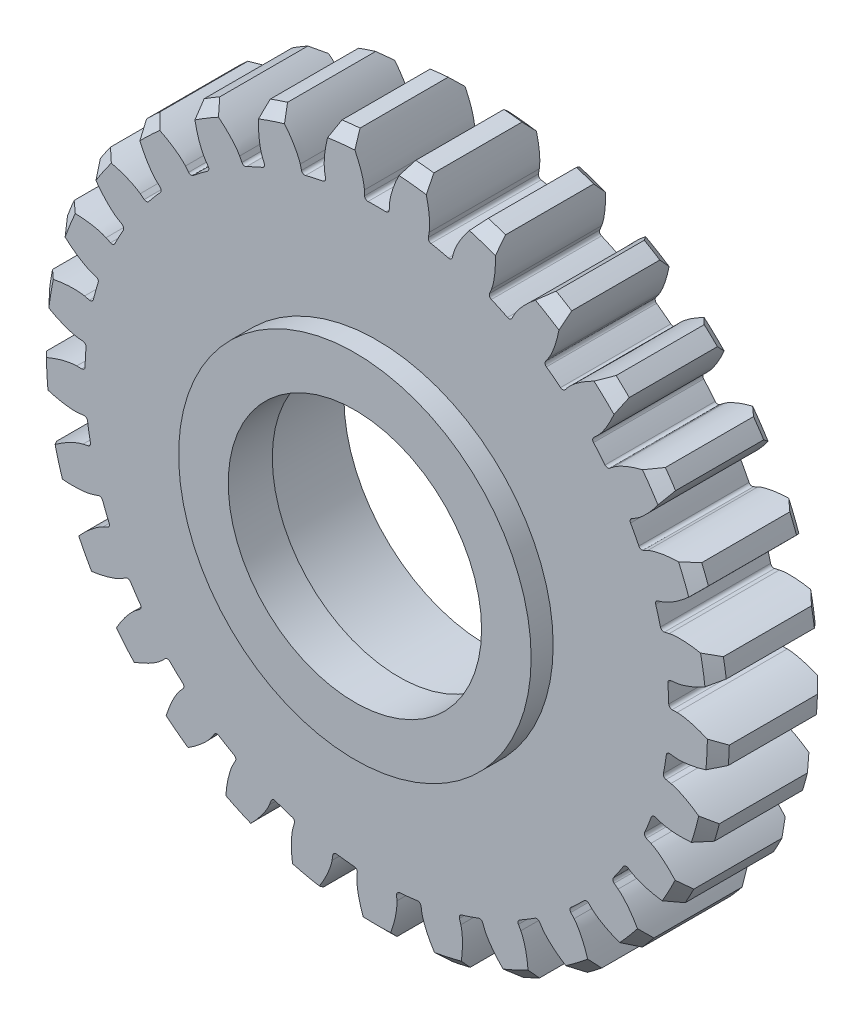
SolidWorks part; units mm, degrees
ref_plane "中间平面" through (0, 0, 0) normal (0, 0, 1) x (1, 0, 0)
ref_plane "上视基准面" through (0, 0, 0) normal (0, 1, 0) x (1, 0, 0)
ref_plane "右视基准面" through (0, 0, 0) normal (1, 0, 0) x (0, 0, -1)
sketch "直齿轮" plane through (0, 0, 0) normal (0, 0, 1) x (1, 0, 0)
  line L0 (0, 0) -> (-1.57, 28.9575) construction
  line L2 (-1.1361, 27.2274) -> (0, 0)
  line L3 (0, 0) -> (0, 52) construction
  line L4 (1.57, 28.9575) -> (0, 0) construction
  line L6 (0, 0) -> (1.1361, 27.2274)
  circle A0 centre (0, 0) radius 27.2511
  circle A1 centre (0, 0) radius 26.5
  arc A2 (1.57, 28.9575) -> (-1.57, 28.9575) centre (0, 0) ccw
  circle A3 centre (0, 0) radius 31
  spline S0 degree 4 poles (-1.1361, 27.2274) (-1.1383, 27.2792) (-1.1458, 27.3825) (-1.1735, 27.5881) (-1.2319, 27.8833) (-1.317, 28.2152) (-1.4592, 28.6714) (-1.6835, 29.2684) (-2.0191, 30.0034) (-2.7, 31.2376) (-3.833, 32.8435) (-5.6838, 34.8744) (-8.4247, 37.0988) (-11.7553, 39.0846) (-15.6046, 40.7081) (-19.6229, 41.843) (-23.7422, 42.5166) (-28.1143, 42.7678) (-33.5316, 42.5127) (-39.9093, 41.3822) (-47.0514, 39.0003) (-53.5517, 35.6404) (-58.7281, 32.1193) (-63.5551, 28.1435) (-67.2707, 24.4825) (-70.6599, 20.5189) (-73.7101, 16.2945) (-75.9427, 12.7746) (-78.4702, 8.2185) (-81.0778, 2.5311) (-83.4938, -4.3624) (-85.0401, -10.9659) (-85.832, -16.1163) (-86.1767, -19.4842) (-86.3032, -21.0404) (-86.3871, -22.3416) (-86.4413, -23.3772) (-86.479, -24.3338) (-86.5037, -25.1739) (-86.5185, -25.9621) (-86.5265, -26.582) (-86.5288, -27.4017) (-86.5259, -27.9867) (-86.5142, -28.9439) (-86.4948, -29.6832) (-86.4665, -30.5837) (-86.4305, -31.3874) (-86.386, -32.2476) (-86.3337, -33.0753) (-86.258, -34.1292) (-86.1512, -35.3815) (-86.0033, -36.8479) (-85.8276, -38.3063) (-85.6573, -39.5568) (-85.5334, -40.3872) (-85.4688, -40.803) (-85.4359, -41.0103) knots 0 0 0 0 0 0.001401 0.002802 0.005604 0.008133 0.010661 0.015718 0.022839 0.02996 0.048734 0.068727 0.096889 0.125051 0.153212 0.181374 0.209535 0.237696 0.271429 0.327752 0.384075 0.440398 0.46856 0.496721 0.553044 0.581206 0.609367 0.637529 0.66569 0.722013 0.778336 0.834659 0.84874 0.86282 0.869861 0.876901 0.883942 0.890982 0.895509 0.900036 0.904564 0.909091 0.914773 0.920455 0.926136 0.931818 0.9375 0.943182 0.948864 0.954545 0.965909 0.977273 0.988636 0.994318 1 1 1 1 1 construction
  spline S1 degree 4 poles (-1.1361, 27.2274) (-1.1383, 27.2792) (-1.1458, 27.3825) (-1.1735, 27.5881) (-1.2319, 27.8833) (-1.317, 28.2152) (-1.4592, 28.6714) (-1.6835, 29.2684) (-2.0191, 30.0034) (-2.7, 31.2376) (-3.833, 32.8435) (-5.6838, 34.8744) (-8.4247, 37.0988) (-11.7553, 39.0846) (-15.6046, 40.7081) (-19.6229, 41.843) (-23.7422, 42.5166) (-28.1143, 42.7678) (-33.5316, 42.5127) (-39.9093, 41.3822) (-47.0514, 39.0003) (-53.5517, 35.6404) (-58.7281, 32.1193) (-63.5551, 28.1435) (-67.2707, 24.4825) (-70.6599, 20.5189) (-73.7101, 16.2945) (-75.9427, 12.7746) (-78.4702, 8.2185) (-81.0778, 2.5311) (-83.4938, -4.3624) (-85.0401, -10.9659) (-85.832, -16.1163) (-86.1767, -19.4842) (-86.3032, -21.0404) (-86.3871, -22.3416) (-86.4413, -23.3772) (-86.479, -24.3338) (-86.5037, -25.1739) (-86.5185, -25.9621) (-86.5265, -26.582) (-86.5281, -27.1599) (-86.5277, -27.4679) (-86.5271, -27.6201) knots 0 0 0 0 0 0.001401 0.002802 0.005604 0.008133 0.010661 0.015718 0.022839 0.02996 0.048734 0.068727 0.096889 0.125051 0.153212 0.181374 0.209535 0.237696 0.271429 0.327752 0.384075 0.440398 0.46856 0.496721 0.553044 0.581206 0.609367 0.637529 0.66569 0.722013 0.778336 0.834659 0.84874 0.86282 0.869861 0.876901 0.883942 0.890982 0.895509 0.900036 0.904564 0.909091 0.909091 0.909091 0.909091 0.909091
  spline S2 degree 4 poles (1.1361, 27.2274) (1.1383, 27.2792) (1.1458, 27.3825) (1.1735, 27.5881) (1.2319, 27.8833) (1.317, 28.2152) (1.4592, 28.6714) (1.6835, 29.2684) (2.0191, 30.0034) (2.7, 31.2376) (3.833, 32.8435) (5.6838, 34.8744) (8.4247, 37.0988) (11.7553, 39.0846) (15.6046, 40.7081) (19.6229, 41.843) (23.7422, 42.5166) (28.1143, 42.7678) (33.5316, 42.5127) (39.9093, 41.3822) (47.0514, 39.0003) (53.5517, 35.6404) (58.7281, 32.1193) (63.5551, 28.1435) (67.2707, 24.4825) (70.6599, 20.5189) (73.7101, 16.2945) (75.9427, 12.7746) (78.4702, 8.2185) (81.0778, 2.5311) (83.4938, -4.3624) (85.0401, -10.9659) (85.832, -16.1163) (86.1767, -19.4842) (86.3032, -21.0404) (86.3871, -22.3416) (86.4413, -23.3772) (86.479, -24.3338) (86.5037, -25.1739) (86.5185, -25.9621) (86.5265, -26.582) (86.5288, -27.4017) (86.5259, -27.9867) (86.5142, -28.9439) (86.4948, -29.6832) (86.4665, -30.5837) (86.4305, -31.3874) (86.386, -32.2476) (86.3337, -33.0753) (86.258, -34.1292) (86.1512, -35.3815) (86.0033, -36.8479) (85.8276, -38.3063) (85.6573, -39.5568) (85.5334, -40.3872) (85.4688, -40.803) (85.4359, -41.0103) knots 0 0 0 0 0 0.001401 0.002802 0.005604 0.008133 0.010661 0.015718 0.022839 0.02996 0.048734 0.068727 0.096889 0.125051 0.153212 0.181374 0.209535 0.237696 0.271429 0.327752 0.384075 0.440398 0.46856 0.496721 0.553044 0.581206 0.609367 0.637529 0.66569 0.722013 0.778336 0.834659 0.84874 0.86282 0.869861 0.876901 0.883942 0.890982 0.895509 0.900036 0.904564 0.909091 0.914773 0.920455 0.926136 0.931818 0.9375 0.943182 0.948864 0.954545 0.965909 0.977273 0.988636 0.994318 1 1 1 1 1 construction
  spline S3 degree 4 poles (1.1361, 27.2274) (1.1383, 27.2792) (1.1458, 27.3825) (1.1735, 27.5881) (1.2319, 27.8833) (1.317, 28.2152) (1.4592, 28.6714) (1.6835, 29.2684) (2.0191, 30.0034) (2.7, 31.2376) (3.833, 32.8435) (5.6838, 34.8744) (8.4247, 37.0988) (11.7553, 39.0846) (15.6046, 40.7081) (19.6229, 41.843) (23.7422, 42.5166) (28.1143, 42.7678) (33.5316, 42.5127) (39.9093, 41.3822) (47.0514, 39.0003) (53.5517, 35.6404) (58.7281, 32.1193) (63.5551, 28.1435) (67.2707, 24.4825) (70.6599, 20.5189) (73.7101, 16.2945) (75.9427, 12.7746) (78.4702, 8.2185) (81.0778, 2.5311) (83.4938, -4.3624) (85.0401, -10.9659) (85.832, -16.1163) (86.1767, -19.4842) (86.3032, -21.0404) (86.3871, -22.3416) (86.4413, -23.3772) (86.479, -24.3338) (86.5037, -25.1739) (86.5185, -25.9621) (86.5265, -26.582) (86.5281, -27.1599) (86.5277, -27.4679) (86.5271, -27.6201) knots 0 0 0 0 0 0.001401 0.002802 0.005604 0.008133 0.010661 0.015718 0.022839 0.02996 0.048734 0.068727 0.096889 0.125051 0.153212 0.181374 0.209535 0.237696 0.271429 0.327752 0.384075 0.440398 0.46856 0.496721 0.553044 0.581206 0.609367 0.637529 0.66569 0.722013 0.778336 0.834659 0.84874 0.86282 0.869861 0.876901 0.883942 0.890982 0.895509 0.900036 0.904564 0.909091 0.909091 0.909091 0.909091 0.909091
  dimension "基圆直径" = 54.5022
  dimension "齿根圆" = 53
  dimension "分度圆" = 58
  dimension "齿顶圆" = 62
  dimension "D1" = 3.1416
sketch "圆" plane through (0, 0, 0) normal (0, 0, 1) x (1, 0, 0)
  circle A0 centre (0, 0) radius 31 construction
  circle A1 centre (0, 0) radius 31
extrude "毛胚" add sketch "圆" along normal mid plane 10
chamfer "轮齿倒角" distance 1 angle 45 2 edges at (31, 0, -5) (31, 0, 5)
sketch "齿形" plane through (0, 0, 0) normal (0, 0, 1) x (1, 0, 0)
  line L4 (0, 0) -> (1.1361, 27.2274) construction
  line L5 (-1.1361, 27.2274) -> (0, 0) construction
  line L6 (0, 0) -> (1.1361, 27.2274)
  line L7 (-1.1361, 27.2274) -> (0, 0)
  circle A4 centre (0, 0) radius 26.5 construction
  circle A5 centre (0, 0) radius 31 construction
  circle A6 centre (0, 0) radius 26.5
  circle A7 centre (0, 0) radius 31
  spline S1 degree 4 poles (-998.7751, 22.5029) (34.2823, 20.2761) (1.8481, 23.0442) (0.7701, 25.5482) (1.2319, 27.8833) (1.317, 28.2152) (1.4592, 28.6714) (1.6835, 29.2684) (2.0191, 30.0034) (2.7, 31.2376) (3.833, 32.8435) (5.6838, 34.8744) (8.4247, 37.0988) (11.7553, 39.0846) (15.6046, 40.7081) (19.6229, 41.843) (23.7422, 42.5166) (28.1143, 42.7678) (33.5316, 42.5127) (39.9093, 41.3822) (47.0514, 39.0003) (53.5517, 35.6404) (58.7281, 32.1193) (63.5551, 28.1435) (67.2707, 24.4825) (70.6599, 20.5189) (73.7101, 16.2945) (75.9427, 12.7746) (78.4702, 8.2185) (81.0778, 2.5311) (83.4938, -4.3624) (85.0401, -10.9659) (85.832, -16.1163) (86.1767, -19.4842) (86.3032, -21.0404) (86.3871, -22.3416) (86.4413, -23.3772) (86.479, -24.3338) (86.5037, -25.1739) (86.5185, -25.9621) (86.5518, -28.539) (86.4636, -34.0277) (86.4797, 8.0602) (82.0766, -1027.4097) knots -0.056197 -0.056197 -0.056197 -0.056197 -0.056197 0.001401 0.002802 0.005604 0.008133 0.010661 0.015718 0.022839 0.02996 0.048734 0.068727 0.096889 0.125051 0.153212 0.181374 0.209535 0.237696 0.271429 0.327752 0.384075 0.440398 0.46856 0.496721 0.553044 0.581206 0.609367 0.637529 0.66569 0.722013 0.778336 0.834659 0.84874 0.86282 0.869861 0.876901 0.883942 0.890982 0.895509 0.900036 0.904564 0.966263 0.966263 0.966263 0.966263 0.966263 only from (1.1361, 27.2274) to (86.5271, -27.6201) construction
  spline S3 degree 4 poles (998.7751, 22.5029) (-34.2823, 20.2761) (-1.8481, 23.0442) (-0.7701, 25.5482) (-1.2319, 27.8833) (-1.317, 28.2152) (-1.4592, 28.6714) (-1.6835, 29.2684) (-2.0191, 30.0034) (-2.7, 31.2376) (-3.833, 32.8435) (-5.6838, 34.8744) (-8.4247, 37.0988) (-11.7553, 39.0846) (-15.6046, 40.7081) (-19.6229, 41.843) (-23.7422, 42.5166) (-28.1143, 42.7678) (-33.5316, 42.5127) (-39.9093, 41.3822) (-47.0514, 39.0003) (-53.5517, 35.6404) (-58.7281, 32.1193) (-63.5551, 28.1435) (-67.2707, 24.4825) (-70.6599, 20.5189) (-73.7101, 16.2945) (-75.9427, 12.7746) (-78.4702, 8.2185) (-81.0778, 2.5311) (-83.4938, -4.3624) (-85.0401, -10.9659) (-85.832, -16.1163) (-86.1767, -19.4842) (-86.3032, -21.0404) (-86.3871, -22.3416) (-86.4413, -23.3772) (-86.479, -24.3338) (-86.5037, -25.1739) (-86.5185, -25.9621) (-86.5518, -28.539) (-86.4636, -34.0277) (-86.4797, 8.0602) (-82.0766, -1027.4097) knots -0.056197 -0.056197 -0.056197 -0.056197 -0.056197 0.001401 0.002802 0.005604 0.008133 0.010661 0.015718 0.022839 0.02996 0.048734 0.068727 0.096889 0.125051 0.153212 0.181374 0.209535 0.237696 0.271429 0.327752 0.384075 0.440398 0.46856 0.496721 0.553044 0.581206 0.609367 0.637529 0.66569 0.722013 0.778336 0.834659 0.84874 0.86282 0.869861 0.876901 0.883942 0.890982 0.895509 0.900036 0.904564 0.966263 0.966263 0.966263 0.966263 0.966263 only from (-1.1361, 27.2274) to (-86.5271, -27.6201) construction
  spline S4 degree 4 poles (1.1361, 27.2274) (1.1383, 27.2792) (1.1458, 27.3825) (1.1735, 27.5881) (1.2319, 27.8833) (1.317, 28.2152) (1.4592, 28.6714) (1.6835, 29.2684) (2.0191, 30.0034) (2.7, 31.2376) (3.833, 32.8435) (5.6838, 34.8744) (8.4247, 37.0988) (11.7553, 39.0846) (15.6046, 40.7081) (19.6229, 41.843) (23.7422, 42.5166) (28.1143, 42.7678) (33.5316, 42.5127) (39.9093, 41.3822) (47.0514, 39.0003) (53.5517, 35.6404) (58.7281, 32.1193) (63.5551, 28.1435) (67.2707, 24.4825) (70.6599, 20.5189) (73.7101, 16.2945) (75.9427, 12.7746) (78.4702, 8.2185) (81.0778, 2.5311) (83.4938, -4.3624) (85.0401, -10.9659) (85.832, -16.1163) (86.1767, -19.4842) (86.3032, -21.0404) (86.3871, -22.3416) (86.4413, -23.3772) (86.479, -24.3338) (86.5037, -25.1739) (86.5185, -25.9621) (86.5265, -26.582) (86.5281, -27.1599) (86.5277, -27.4679) (86.5271, -27.6201) knots 0 0 0 0 0 0.001401 0.002802 0.005604 0.008133 0.010661 0.015718 0.022839 0.02996 0.048734 0.068727 0.096889 0.125051 0.153212 0.181374 0.209535 0.237696 0.271429 0.327752 0.384075 0.440398 0.46856 0.496721 0.553044 0.581206 0.609367 0.637529 0.66569 0.722013 0.778336 0.834659 0.84874 0.86282 0.869861 0.876901 0.883942 0.890982 0.895509 0.900036 0.904564 0.909091 0.909091 0.909091 0.909091 0.909091
  spline S5 degree 4 poles (-1.1361, 27.2274) (-1.1383, 27.2792) (-1.1458, 27.3825) (-1.1735, 27.5881) (-1.2319, 27.8833) (-1.317, 28.2152) (-1.4592, 28.6714) (-1.6835, 29.2684) (-2.0191, 30.0034) (-2.7, 31.2376) (-3.833, 32.8435) (-5.6838, 34.8744) (-8.4247, 37.0988) (-11.7553, 39.0846) (-15.6046, 40.7081) (-19.6229, 41.843) (-23.7422, 42.5166) (-28.1143, 42.7678) (-33.5316, 42.5127) (-39.9093, 41.3822) (-47.0514, 39.0003) (-53.5517, 35.6404) (-58.7281, 32.1193) (-63.5551, 28.1435) (-67.2707, 24.4825) (-70.6599, 20.5189) (-73.7101, 16.2945) (-75.9427, 12.7746) (-78.4702, 8.2185) (-81.0778, 2.5311) (-83.4938, -4.3624) (-85.0401, -10.9659) (-85.832, -16.1163) (-86.1767, -19.4842) (-86.3032, -21.0404) (-86.3871, -22.3416) (-86.4413, -23.3772) (-86.479, -24.3338) (-86.5037, -25.1739) (-86.5185, -25.9621) (-86.5265, -26.582) (-86.5281, -27.1599) (-86.5277, -27.4679) (-86.5271, -27.6201) knots 0 0 0 0 0 0.001401 0.002802 0.005604 0.008133 0.010661 0.015718 0.022839 0.02996 0.048734 0.068727 0.096889 0.125051 0.153212 0.181374 0.209535 0.237696 0.271429 0.327752 0.384075 0.440398 0.46856 0.496721 0.553044 0.581206 0.609367 0.637529 0.66569 0.722013 0.778336 0.834659 0.84874 0.86282 0.869861 0.876901 0.883942 0.890982 0.895509 0.900036 0.904564 0.909091 0.909091 0.909091 0.909091 0.909091
extrude "插齿" cut sketch "齿形" against normal mid plane 10 contours S5 A6 S4 A7 region at (0, 29.0778, 0)
fillet "圆角1" [suppressed] radius 0.3
pattern_circular "圆周阵列1" [suppressed] count 29 over 360 of bodies 165
fillet "圆角2" radius 0.3 2 edges at (1.1048, 26.477, 0) (-1.1048, 26.477, 0)
pattern_circular "圆周阵列2" count 29 over 360 about axis through (0, 0, 5) along (0, 0, -1) of "圆角2", "插齿"
sketch "分度圆" plane through (0, 0, 0) normal (0, 0, 1) x (1, 0, 0)
  circle A0 centre (0, 0) radius 29 construction
  circle A1 centre (0, 0) radius 29 construction
sketch "草图1" plane through (0, 0, 5) normal (0, 0, 1) x (1, 0, 0)
  circle A0 centre (0, 0) radius 16
  dimension "D1" = 32
extrude "凸台-拉伸1" add sketch "草图1" along normal blind 2
sketch "草图2" plane through (0, 0, 7) normal (0, 0, 1) x (1, 0, 0)
  circle A0 centre (0, 0) radius 11.5
  dimension "D1" = 23
extrude "切除-拉伸1" cut sketch "草图2" against normal through all
sketch "草图3" plane through (0, 0, -5) normal (0, 0, -1) x (-1, 0, 0)
  circle A0 centre (0, 0) radius 13
  dimension "D1" = 26
extrude "切除-拉伸2" cut sketch "草图3" against normal blind 8
equation "\"m\"= 2'模数"
equation "\"z\" = 29'齿数"
equation "\"a\"= 20'压力角（常见为20°）"
equation "\"B\" = 10'齿宽"
equation "\"C1\"= 1'轮齿倒角（若设为0，则无倒角）"
equation "\"x\"= 0'变位系数（不懂勿动）"
equation "\"ha\"= 1'齿顶高系数（不懂勿动）"
equation "\"c\"= 0.25'顶隙系数（不懂勿动）"
equation "\"基圆直径@直齿轮\"= \"m\" * \"z\" * cos ( \"a\" )"
equation "\"齿根圆@直齿轮\" = \"m\" * ( \"z\" - 2 * ( \"ha\" - \"x\" + \"c\" ) )"
equation "\"分度圆@直齿轮\"=\"m\" * \"z\""
equation "\"齿顶圆@直齿轮\" = \"m\" * ( \"z\" + 2 * ( \"ha\" + \"x\" ) )"
equation "\"R\"= 0.3'齿根圆角"
equation "\"D1\"= \"R\""
equation "\"D1@毛胚\" = \"B\""
equation "\"D1@轮齿倒角\" = IIF ( \"C1\" > 0 , \"C1\" , 0.001 )"
equation "\"轮齿倒角\"= IIF ( \"C1\" > 0 , \"unsuppressed\" , \"suppressed\" )"
equation "\"D1@插齿\" = \"B\""
equation "\"D1@圆周阵列1\" = \"z\""
equation "\"D1@直齿轮\"= \"m\" * ( pi / 2 ) - 2 * \"m\" * tan ( \"a\" ) * \"x\"'作者：机械菌-"
equation "\"D1@圆角1\"=\"R\""
equation "\"圆角1\" = IIF ( \"m\" * ( \"z\" - 2 * ( \"ha\" - \"x\" + \"c\" ) ) > \"m\" * \"z\" * cos ( \"a\" ) , \"unsuppressed\" , \"suppressed\" )"
equation "\"圆周阵列1\"= IIF ( \"m\" * ( \"z\" - 2 * ( \"ha\" - \"x\" + \"c\" ) ) > \"m\" * \"z\" * cos ( \"a\" ) , \"unsuppressed\" , \"suppressed\" )"
equation "\"D1@圆角2\"=\"R\""
equation "\"D1@圆周阵列2\" = \"z\""
equation "\"圆角2\" = IIF ( \"m\" * ( \"z\" - 2 * ( \"ha\" - \"x\" + \"c\" ) ) < \"m\" * \"z\" * cos ( \"a\" ) , \"unsuppressed\" , \"suppressed\" )"
equation "\"圆周阵列2\"= IIF ( \"m\" *  ( \"z\" - 2 *  ( \"ha\" - \"x\" + \"c\" )  )  < \"m\" * \"z\" * cos ( \"a\" )  ,  unsuppressed  ,  suppressed  ) "
